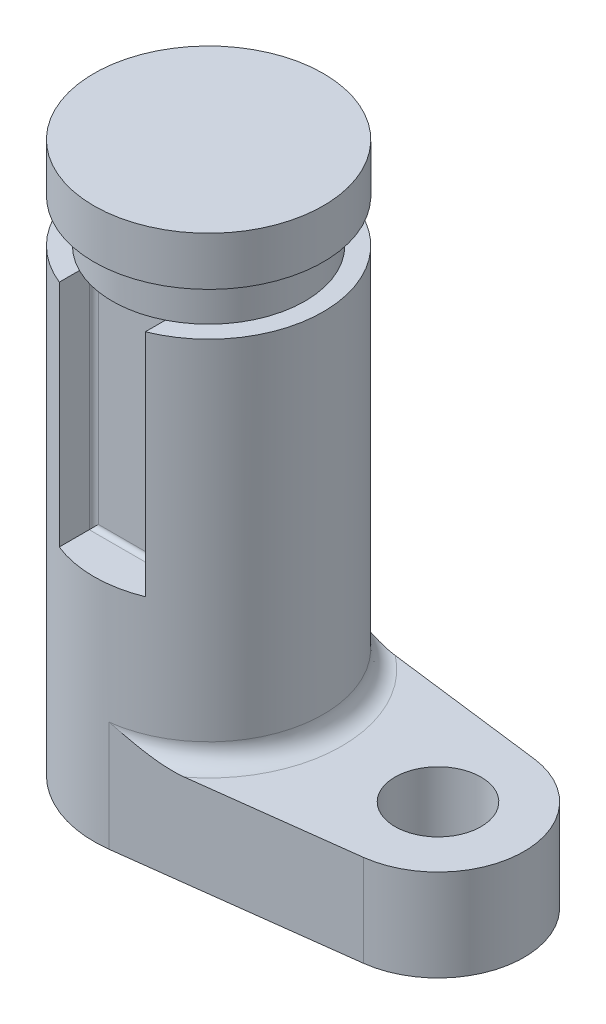
SolidWorks part; units mm, degrees
material "AISI 1015 Steel, Cold Drawn (SS)"
ref_plane "Front Plane" through (0, 0, 0) normal (0, 0, 1) x (1, 0, 0)
ref_plane "Top Plane" through (0, 0, 0) normal (0, 1, 0) x (1, 0, 0)
ref_plane "Right Plane" through (0, 0, 0) normal (1, 0, 0) x (0, 0, -1)
sketch "Sketch1" plane through (0, 0, 0) normal (0, 1, 0) x (1, 0, 0)
  circle A0 centre (0, 0) radius 3.175
  dimension "D1" = 6.35
extrude "Boss-Extrude1" add sketch "Sketch1" along normal blind 12.7
sketch "Sketch2" plane through (0, 0, 0) normal (0, -1, 0) x (1, 0, 0)
  line L0 (-10.6761, 0) -> (14.4716, 0) construction
  line L1 (0.3969, 3.1501) -> (6.6477, 2.3626)
  line L2 (6.6477, -2.3626) -> (0.3969, -3.1501)
  circle A0 centre (6.35, 0) radius 1.1906
  circle A1 centre (0, 0) radius 3.175 construction
  arc A2 (6.6477, 2.3626) -> (6.6477, -2.3626) centre (6.35, 0) cw
  circle M4 centre (0, 0) radius 3.175
  dimension "D2" = 2.3813
  dimension "D3" = 2.3813
  dimension "D1" = 6.35
extrude "Boss-Extrude2" add sketch "Sketch2" along normal blind 2.54 contours L0 M4 | L0 A0 A2 L1 M4 | L0 L2 A2 A0 M4 | L0 M4 region at (0, 0, 1.3475) region at (0, 0, -1.3475) region at (5.108, 0, 1.4695) region at (5.108, 0, -1.4695)
fillet "Fillet1" radius 0.508 1 edges at (3.175, 0, 0)
sketch "Sketch3" plane through (0, 0, 0) normal (0, 1, 0) x (1, 0, 0)
  line L0 (0, -5.1656) -> (0, 6.1347) construction
  line L1 (-6.2309, 0) -> (11.0317, 0) construction
  line L3 (-1.1906, -4.3637) -> (1.1906, -4.3637)
  line L4 (-1.1906, -4.3637) -> (-1.1906, -1.9863)
  line L5 (-1.1906, -1.9863) -> (1.1906, -1.9863)
  line L6 (1.1906, -4.3637) -> (1.1906, -1.9863)
  line L7 (-1.1906, -4.3637) -> (1.1906, -1.9863) construction
  line L8 (-1.1906, -1.9863) -> (1.1906, -4.3637) construction
  arc A0 (0.3969, 3.1501) -> (0.3969, -3.1501) centre (0, 0) ccw construction
  point P5 (0, -3.175)
  dimension "D1" = 1.1887
  dimension "D2" = 2.3813
extrude "Cut-Extrude2" cut sketch "Sketch3" along normal blind 6.35 from offset 3.81
fillet "Fillet4" radius 0.127 4 edges at (-1.1906, 6.985, 1.9863) (1.1906, 6.985, 1.9863) (0, 3.81, 1.9863) (0, 10.16, 1.9863)
ref_plane "Plane1" through (0, 10.16, 0) normal (0, 1, 0) x (1, 0, 0)
sketch "Sketch5" plane through (0, 10.16, 0) normal (0, 1, 0) x (1, 0, 0)
  circle A0 centre (0, 0) radius 2.667
  dimension "D1" = 5.334
extrude "Cut-Extrude3" cut sketch "Sketch5" along normal blind 1.1938 flip side to cut
equation "\"0.3n\"=0.4"
